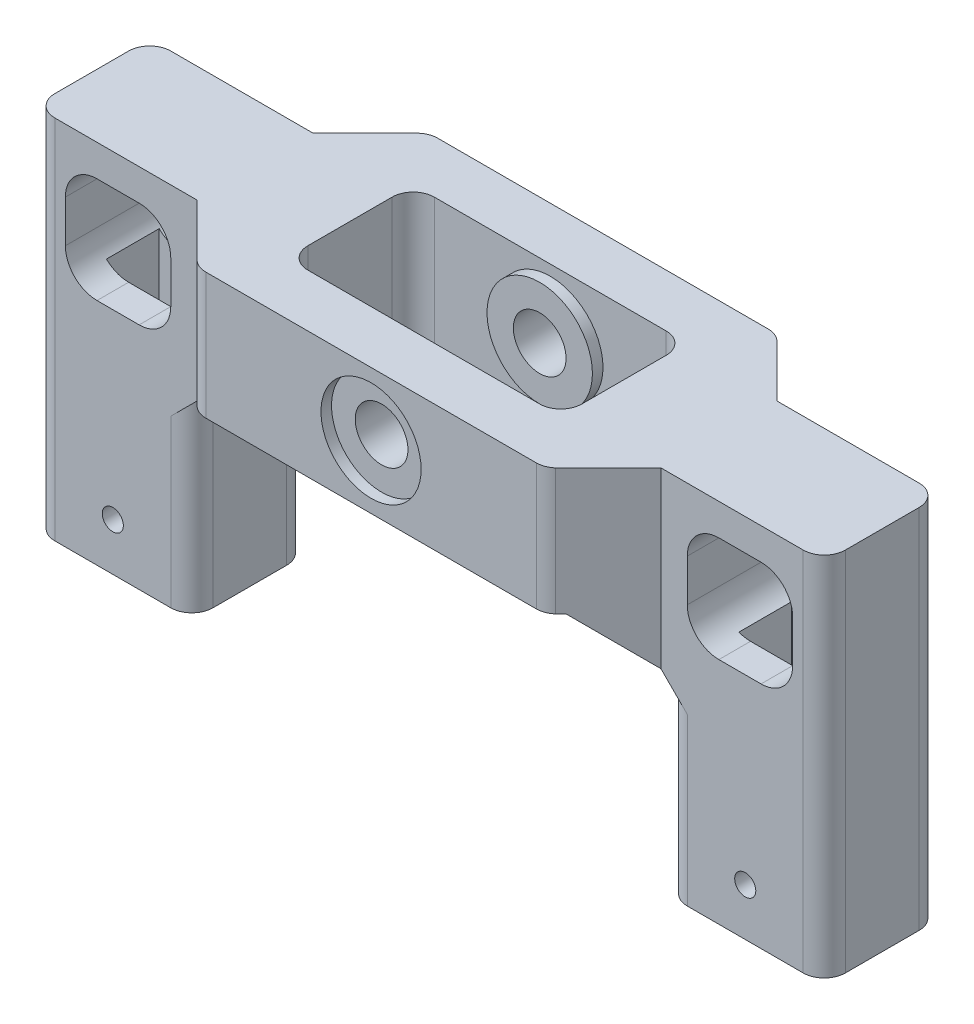
SolidWorks part; units mm, degrees
material "聚脂树脂"
ref_plane "前视基准面" through (0, 0, 0) normal (0, 0, 1) x (1, 0, 0)
ref_plane "上视基准面" through (0, 0, 0) normal (0, 1, 0) x (1, 0, 0)
ref_plane "右视基准面" through (0, 0, 0) normal (1, 0, 0) x (0, 0, -1)
other "Configuration Table"
sketch "草图1" plane through (0, 0, 0) normal (0, 0, 1) x (1, 0, 0)
  line L0 (0, 0) -> (63.4535, 0) construction
  line L5 (-22.5, 12.25) -> (-37.5, -12.25) construction
  line L6 (22.5, -12.25) -> (37.5, -12.25)
  line L7 (0, 0) -> (0, 35.1803) construction
  line L8 (22.5, -12.25) -> (22.5, 12.25)
  line L9 (22.5, 12.25) -> (37.5, 12.25)
  line L10 (37.5, -12.25) -> (37.5, 12.25)
  line L11 (22.5, -12.25) -> (37.5, 12.25) construction
  line L12 (22.5, 12.25) -> (37.5, -12.25) construction
  line L13 (-22.5, -12.25) -> (-37.5, 12.25) construction
  line L14 (-37.5, -12.25) -> (-37.5, 12.25)
  line L15 (-22.5, 12.25) -> (-37.5, 12.25)
  line L16 (-22.5, -12.25) -> (-22.5, 12.25)
  line L17 (-22.5, -12.25) -> (-37.5, -12.25)
  point P0 (30, 0)
  point P21 (-30, 0)
  dimension "D3" = 30
  dimension "D1" = 15
  dimension "D2" = 24.5
extrude "凸台-拉伸1" add sketch "草图1" along normal blind 5.5 and the other way blind 5.5
sketch "草图2" plane through (0, 12.25, 0) normal (0, 1, 0) x (1, 0, 0)
  line L0 (0, 0) -> (0, 28.9204) construction
  line L1 (0, 0) -> (49.6088, 0) construction
  line L2 (-26.4, 2.5) -> (-33.6, -2.5) construction
  line L3 (26.4, -2.5) -> (33.6, -2.5)
  line L4 (26.4, -2.5) -> (26.4, 2.5)
  line L5 (26.4, 2.5) -> (33.6, 2.5)
  line L6 (33.6, -2.5) -> (33.6, 2.5)
  line L7 (26.4, -2.5) -> (33.6, 2.5) construction
  line L8 (26.4, 2.5) -> (33.6, -2.5) construction
  line L9 (-26.4, -2.5) -> (-33.6, 2.5) construction
  line L10 (-33.6, -2.5) -> (-33.6, 2.5)
  line L11 (-26.4, 2.5) -> (-33.6, 2.5)
  line L12 (-26.4, -2.5) -> (-26.4, 2.5)
  line L13 (-26.4, -2.5) -> (-33.6, -2.5)
  point P3 (30, 0)
  point P13 (-30, 0)
  dimension "D1" = 7.2
  dimension "D2" = 5
  dimension "D3" = 30
extrude "切除-拉伸1" cut sketch "草图2" against normal blind 62
sketch "草图3" plane through (0, 12.25, 0) normal (0, 1, 0) x (1, 0, 0)
  line L0 (0, 0) -> (46.7542, 0) construction
  line L1 (0, 0) -> (0, 26.73) construction
  line L2 (22.5, 5.5) -> (17, 5.5)
  line L3 (17, 5.5) -> (17, 11)
  line L4 (17, 11) -> (-17, 11)
  line L6 (-13, 6) -> (13, 6)
  line L7 (13, 6) -> (13, -6)
  line L8 (22.5, 5.5) -> (22.5, -5.5)
  line L9 (22.5, 5.5) -> (22.5, -5.5) construction
  line L10 (-13, -6) -> (13, -6)
  line L12 (17, -11) -> (-17, -11)
  line L13 (17, -5.5) -> (17, -11)
  line L14 (22.5, -5.5) -> (17, -5.5)
  line L15 (-22.5, -5.5) -> (-17, -5.5)
  line L16 (-17, -5.5) -> (-17, -11)
  line L17 (-22.5, 5.5) -> (-22.5, -5.5)
  line L18 (-13, 6) -> (-13, -6)
  line L19 (-17, 5.5) -> (-17, 11)
  line L20 (-22.5, 5.5) -> (-17, 5.5)
  point P16 (22.5, 0)
  point P17 (13, 0)
  point P24 (0, -11)
  point P25 (0, -6)
  point P27 (0, 6)
  point P28 (0, 11)
  point P29 (-13, 0)
  point P30 (-22.5, 0)
  dimension "D1" = 12
  dimension "D2" = 26
  dimension "D3" = 34
  dimension "D4" = 22
extrude "凸台-拉伸2" add sketch "草图3" against normal blind 12
sketch "草图4" plane through (0, 0, 11) normal (0, 0, 1) x (1, 0, 0)
  line L0 (0, 0) -> (0, 29.922) construction
  line L1 (-17, 0.25) -> (17, 0.25) construction
  circle A0 centre (0, 6.25) radius 2.5
  dimension "D1" = 5
  dimension "D2" = 6
extrude "切除-拉伸2" cut sketch "草图4" against normal blind 90
sketch "草图6" plane through (0, 0, 5.5) normal (0, 0, 1) x (1, 0, 0)
  line L0 (0, 0) -> (0, 28.8184) construction
  line L1 (0, 0) -> (51.072, 0) construction
  line L2 (-37.5, 12.25) -> (-37.5, 24.25)
  line L3 (-37.5, 24.25) -> (-16, 24.25)
  line L4 (-16, 24.25) -> (-16, 12.25)
  line L5 (-37.5, 12.25) -> (-17, 12.25) construction
  line L7 (-35, 12.25) -> (-35, 21.75)
  line L8 (-35, 21.75) -> (-18.5, 21.75)
  line L9 (-18.5, 21.75) -> (-18.5, 12.25)
  line L10 (-37.5, 12.25) -> (-35, 12.25)
  line L11 (-18.5, 12.25) -> (-16, 12.25)
  line L12 (18.5, 21.75) -> (18.5, 12.25)
  line L13 (35, 21.75) -> (18.5, 21.75)
  line L14 (35, 12.25) -> (35, 21.75)
  line L15 (37.5, 12.25) -> (35, 12.25)
  line L16 (37.5, 12.25) -> (37.5, 24.25)
  line L17 (37.5, 24.25) -> (16, 24.25)
  line L18 (16, 24.25) -> (16, 12.25)
  line L19 (18.5, 12.25) -> (16, 12.25)
  line L20 (37.5, 12.25) -> (17, 12.25) construction
  dimension "D1" = 12
  dimension "D3" = 32
  dimension "D2" = 2.5
chamfer "倒角2" distance 5 angle 45 4 edges at (17, 6.25, -5.5) (-17, 6.25, -5.5) (17, 6.25, 5.5) (-17, 6.25, 5.5)
fillet "圆角2" radius 2 8 edges at (17, 6.25, 11) (-17, 6.25, 11) (-17, 6.25, -11) (17, 6.25, -11) (-13, 6.25, 6) (13, 6.25, 6) (13, 6.25, -6) (-13, 6.25, -6)
sketch "草图14" plane through (0, -12.25, 0) normal (0, -1, 0) x (1, 0, 0)
  line L0 (26.4, 2.5) -> (26.4, -2.5) construction
  line L1 (26.4, -2.5) -> (33.6, -2.5) construction
  line L2 (33.6, -2.5) -> (33.6, 2.5) construction
  line L3 (33.6, 2.5) -> (26.4, 2.5) construction
  line L4 (-22.5, -5.5) -> (-22.5, 5.5)
  line L5 (-22.5, 5.5) -> (-37.5, 5.5)
  line L6 (-37.5, 5.5) -> (-37.5, -5.5)
  line L7 (-37.5, -5.5) -> (-22.5, -5.5)
  line L8 (-22.5, -5.5) -> (-22.5, 5.5)
  line L9 (-22.5, 5.5) -> (-37.5, 5.5)
  line L10 (-37.5, 5.5) -> (-37.5, -5.5)
  line L11 (-37.5, -5.5) -> (-22.5, -5.5)
  line L12 (37.5, -5.5) -> (37.5, 5.5)
  line L13 (37.5, 5.5) -> (22.5, 5.5)
  line L14 (22.5, 5.5) -> (22.5, -5.5)
  line L15 (22.5, -5.5) -> (37.5, -5.5)
  line L16 (37.5, -5.5) -> (37.5, 5.5)
  line L17 (37.5, 5.5) -> (22.5, 5.5)
  line L18 (22.5, 5.5) -> (22.5, -5.5)
  line L19 (22.5, -5.5) -> (37.5, -5.5)
  line L20 (-26.4, -2.5) -> (-26.4, 2.5) construction
  line L21 (-33.6, -2.5) -> (-26.4, -2.5) construction
  line L22 (-33.6, 2.5) -> (-33.6, -2.5) construction
  line L23 (-26.4, 2.5) -> (-33.6, 2.5) construction
  line L24 (26.4, 2.5) -> (26.4, -2.5)
  line L25 (26.4, -2.5) -> (33.6, -2.5)
  line L26 (33.6, -2.5) -> (33.6, 2.5)
  line L27 (33.6, 2.5) -> (26.4, 2.5)
  line L28 (-26.4, -2.5) -> (-26.4, 2.5)
  line L29 (-33.6, -2.5) -> (-26.4, -2.5)
  line L30 (-33.6, 2.5) -> (-33.6, -2.5)
  line L31 (-26.4, 2.5) -> (-33.6, 2.5)
  dimension "D1" = 0
  dimension "D2" = 0
extrude "凸台-拉伸5" add sketch "草图14" along normal blind 10.25
sketch "草图7" plane through (0, 0, 5.5) normal (0, 0, 1) x (1, 0, 0)
  line L0 (0, 0) -> (0, 26.3753) construction
  line L1 (0, 1.8) -> (49.2666, 1.8) construction
  line L2 (0, 0) -> (53.2402, 0) construction
  circle A0 centre (30, -18) radius 1
  circle A3 centre (-30, -18) radius 1
  dimension "D1" = 60
  dimension "D2" = 18
  dimension "D3" = 2
  dimension "D6" = 2
  dimension "D7" = 30
  dimension "D4" = 1.8
  dimension "D5" = 30
extrude "切除-拉伸3" cut sketch "草图7" against normal blind 34
sketch "草图9" plane through (0, 0, 5.5) normal (0, 0, 1) x (1, 0, 0)
  line L6 (0, 0) -> (0, -19.4283) construction
sketch "草图13" plane through (0, 0, -6) normal (0, 0, 1) x (1, 0, 0)
  circle A0 centre (0, 6.25) radius 5
  circle A1 centre (0, 6.25) radius 2.5
  dimension "D1" = 5
  dimension "D2" = 10
extrude "凸台-拉伸4" add sketch "草图13" along normal blind 1
mirror "镜向1" about plane through (0, 0, 0) normal (0, 0, 1) of "凸台-拉伸4"
chamfer "倒角3" distance 5 angle 45 2 edges at (22.5, 0.25, 0) (-22.5, 0.25, 0)
sketch "草图17" plane through (0, 0, 11) normal (0, 0, 1) x (1, 0, 0)
  circle A0 centre (0, 6.25) radius 2.5
  circle A1 centre (0, 6.25) radius 4.75
  dimension "D1" = 5
  dimension "D2" = 9.5
sketch "草图19" plane through (0, 0, 5.5) normal (0, 0, 1) x (1, 0, 0)
  line L0 (-37.5, 12.25) -> (-37.5, -22.5) construction
  line L1 (-34.5, -0.75) -> (-24.5, -0.75)
  line L2 (-34.5, -0.75) -> (-34.5, 9.25)
  line L3 (-34.5, 9.25) -> (-24.5, 9.25)
  line L4 (-24.5, -0.75) -> (-24.5, 9.25)
  line L5 (-34.5, -0.75) -> (-24.5, 9.25) construction
  line L6 (-34.5, 9.25) -> (-24.5, -0.75) construction
  line L8 (0, 6.25) -> (0, 20.5388) construction
  line L9 (-37.5, 12.25) -> (-22, 12.25) construction
  line L10 (34.5, 9.25) -> (24.5, 9.25)
  line L11 (24.5, -0.75) -> (24.5, 9.25)
  line L12 (34.5, -0.75) -> (24.5, -0.75)
  line L13 (34.5, -0.75) -> (34.5, 9.25)
  point P0 (-29.5, 4.25)
  dimension "D1" = 10
  dimension "D2" = 10
  dimension "D3" = 3
  dimension "D4" = 3
extrude "切除-拉伸4" cut sketch "草图19" against normal blind 31.2 contours L3 L2 L1 L4 | L10 L11 L12 L13 region at (-29.5, 4.25, 5.5) region at (29.5, 4.25, 5.5)
extrude "切除-拉伸5" cut sketch "草图17" against normal blind 1
mirror "镜向2" about plane through (0, 0, 0) normal (0, 0, 1) of "切除-拉伸5"
sketch "草图20" plane through (0, 0, -2.5) normal (0, 0, 1) x (1, 0, 0)
  line L4 (-33.6, 12.25) -> (-33.6, 9.25)
  line L5 (-33.6, 9.25) -> (-26.4, 9.25)
  line L6 (-26.4, 9.25) -> (-26.4, 12.25)
  line L7 (-26.4, 12.25) -> (-33.6, 12.25)
  line L8 (-33.6, 12.25) -> (-33.6, 9.25)
  line L10 (-26.4, 9.25) -> (-26.4, 12.25)
  line L11 (-26.4, 12.25) -> (-33.6, 12.25)
  line L12 (26.4, 9.25) -> (33.6, 9.25)
  line L13 (33.6, 9.25) -> (33.6, 12.25)
  line L14 (33.6, 12.25) -> (26.4, 12.25)
  line L15 (26.4, 12.25) -> (26.4, 9.25)
  line L17 (33.6, 9.25) -> (33.6, 12.25)
  line L18 (33.6, 12.25) -> (26.4, 12.25)
  line L19 (26.4, 12.25) -> (26.4, 9.25)
  line L24 (-33.6, 9.25) -> (-26.4, 9.25)
  line L25 (26.4, 9.25) -> (33.6, 9.25)
  dimension "D1" = 0
  dimension "D2" = 0
extrude "凸台-拉伸6" add sketch "草图20" along normal up to surface (5 mm away) up to face at (-29, -18, 2.5)
fillet "圆角6" radius 3 8 edges at (24.5, -0.75, 0) (-24.5, -0.75, 0) (34.5, -0.75, 0) (24.5, 9.25, 0) (34.5, 9.25, 0) (-24.5, 9.25, 0) (-34.5, 9.25, 0) (-34.5, -0.75, 0)
fillet "圆角7" radius 2 8 edges at (-22.5, -13.625, -5.5) (37.5, -5.125, -5.5) (37.5, -5.125, 5.5) (22.5, -13.625, -5.5) (22.5, -13.625, 5.5) (-37.5, -5.125, -5.5) (-22.5, -13.625, 5.5) (-37.5, -5.125, 5.5)
equation "\"5】\"=10"
